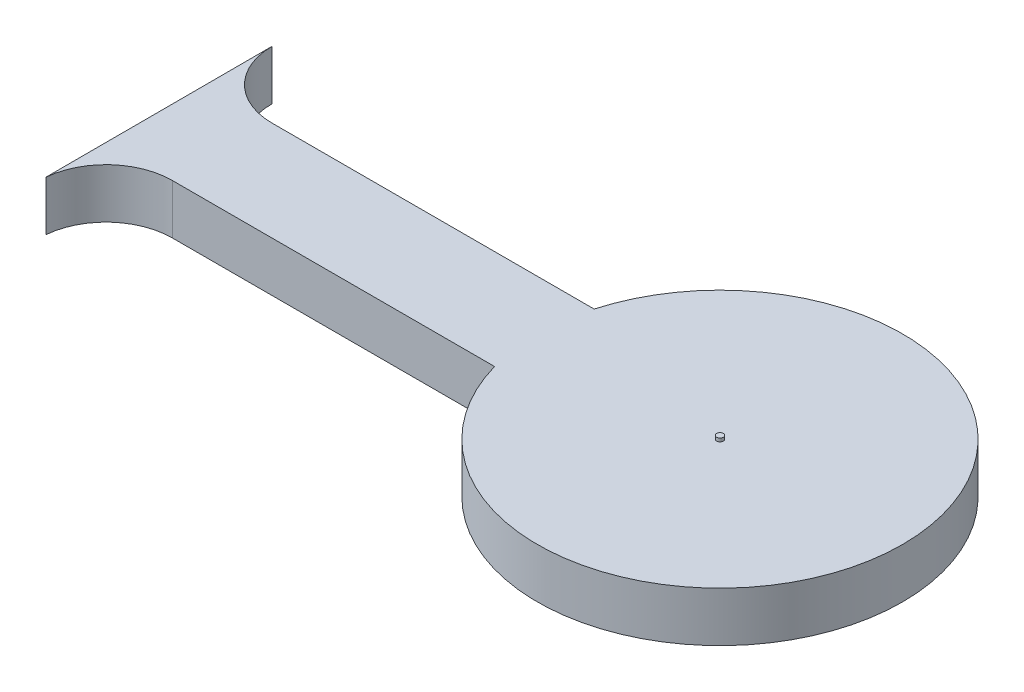
SolidWorks part; units mm, degrees
ref_plane "Plano frontal" through (0, 0, 0) normal (0, 0, 1) x (1, 0, 0)
ref_plane "Plano superior" through (0, 0, 0) normal (0, 1, 0) x (1, 0, 0)
ref_plane "Plano direito" through (0, 0, 0) normal (1, 0, 0) x (0, 0, -1)
sketch "Esboço1" plane through (0, 0, 0) normal (0, 1, 0) x (1, 0, 0)
  line L0 (0, 0) -> (9.7085, 0)
  line L2 (0, 3) -> (9.7085, 3)
  line L3 (-2, 5) -> (-1.9916, -1.8166)
  arc A0 (9.7085, 3) -> (9.7085, 0) centre (15, 1.5) cw
  arc A1 (-2, 5) -> (0, 3) centre (0, 5) ccw
  arc A2 (0, 0) -> (-1.9916, -1.8166) centre (0, -2) ccw
  dimension "D1" = 5.5
  dimension "D5" = 4
  dimension "D6" = 4
  dimension "D2" = 3
  dimension "D3" = 1.5
  dimension "D4" = 15
extrude "Ressalto-extrusão1" add sketch "Esboço1" along normal blind 1.5
sketch "Esboço2" plane through (0, 1.5, 0) normal (0, 1, 0) x (1, 0, 0)
  circle A0 centre (15, 1.5) radius 0.1
extrude "Ressalto-extrusão2" add sketch "Esboço2" along normal blind 0.1
